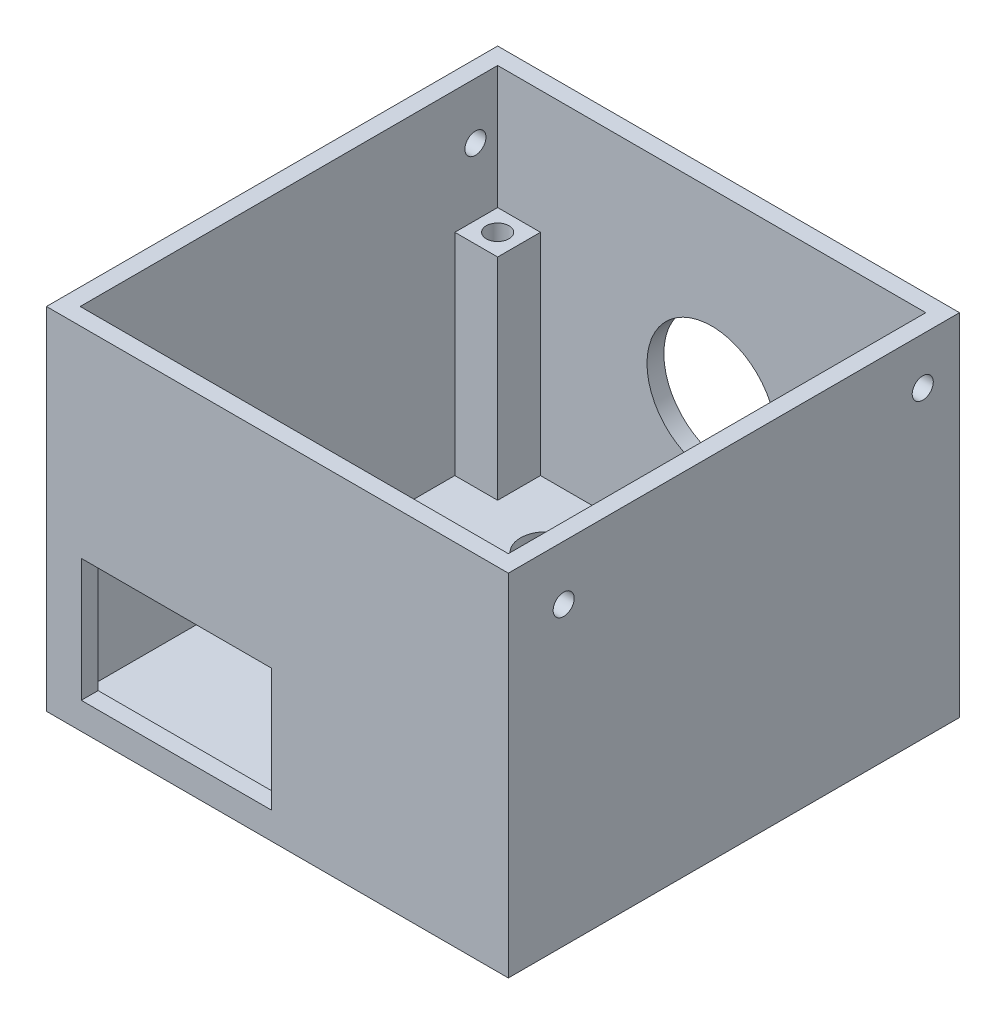
SolidWorks part; units mm, degrees
ref_plane "Front Plane" through (0, 0, 0) normal (0, 0, 1) x (1, 0, 0)
ref_plane "Top Plane" through (0, 0, 0) normal (0, 1, 0) x (1, 0, 0)
ref_plane "Right Plane" through (0, 0, 0) normal (1, 0, 0) x (0, 0, -1)
sketch "Sketch1" plane through (0, 0, 0) normal (0, 1, 0) x (1, 0, 0)
  line L1 (27.4, -26.765) -> (-27.4, -26.765)
  line L2 (27.4, -26.765) -> (27.4, 26.765)
  line L3 (27.4, 26.765) -> (-27.4, 26.765)
  line L4 (-27.4, -26.765) -> (-27.4, 26.765)
  line L5 (27.4, -26.765) -> (-27.4, 26.765) construction
  line L6 (27.4, 26.765) -> (-27.4, -26.765) construction
  point P0 (0, 0)
  dimension "D1" = 54.8
  dimension "D2" = 53.53
extrude "Boss-Extrude1" add sketch "Sketch1" along normal blind 41.6
sketch "Sketch2" plane through (0, 41.6, 0) normal (0, 1, 0) x (1, 0, 0)
  line L0 (-27.4, 26.765) -> (-27.4, -26.765) construction
  line L1 (25.4, -24.765) -> (-25.4, -24.765)
  line L2 (25.4, -24.765) -> (25.4, 24.765)
  line L3 (25.4, 24.765) -> (-25.4, 24.765)
  line L4 (-25.4, -24.765) -> (-25.4, 24.765)
  line L5 (25.4, -24.765) -> (-25.4, 24.765) construction
  line L6 (25.4, 24.765) -> (-25.4, -24.765) construction
  line L7 (27.4, 26.765) -> (-27.4, 26.765) construction
  point P0 (0, 0)
  dimension "D1" = 2
  dimension "D2" = 2
extrude "Cut-Extrude1" cut sketch "Sketch2" against normal blind 39.6
sketch "Sketch3" plane through (0, 2, 0) normal (0, 1, 0) x (1, 0, 0)
  line L1 (-25.4, 24.765) -> (-20.32, 24.765)
  line L2 (-25.4, 24.765) -> (-25.4, 19.685)
  line L3 (-25.4, 19.685) -> (-20.32, 19.685)
  line L4 (-20.32, 24.765) -> (-20.32, 19.685)
  line L5 (25.4, 24.765) -> (20.32, 24.765)
  line L6 (25.4, 24.765) -> (25.4, 19.685)
  line L7 (25.4, 19.685) -> (20.32, 19.685)
  line L8 (20.32, 24.765) -> (20.32, 19.685)
  line L9 (25.4, -24.765) -> (20.32, -24.765)
  line L10 (25.4, -24.765) -> (25.4, -19.685)
  line L11 (25.4, -19.685) -> (20.32, -19.685)
  line L12 (20.32, -24.765) -> (20.32, -19.685)
  dimension "D1" = 5.08
  dimension "D2" = 5.08
  dimension "D3" = 5.08
  dimension "D4" = 5.08
  dimension "D5" = 5.08
  dimension "D6" = 5.08
extrude "Boss-Extrude2" add sketch "Sketch3" along normal blind 25
sketch "Sketch4" plane through (0, 27, 0) normal (0, 1, 0) x (1, 0, 0)
  line L0 (-20.32, 19.685) -> (-20.32, 24.765) construction
  line L3 (-25.4, 19.685) -> (-20.32, 19.685) construction
  line L4 (20.32, 19.685) -> (25.4, 19.685) construction
  line L5 (20.32, 24.765) -> (20.32, 19.685) construction
  line L6 (25.4, -19.685) -> (20.32, -19.685) construction
  line L7 (20.32, -19.685) -> (20.32, -24.765) construction
  circle A0 centre (-22.86, 22.225) radius 1.35
  circle A1 centre (22.86, 22.225) radius 1.35
  circle A2 centre (22.86, -22.225) radius 1.35
  point P12 (22.86, -19.685)
  dimension "D1" = 2.54
  dimension "D3" = 2.54
  dimension "D5" = 2.54
  dimension "D2" = 2.54
  dimension "D4" = 2.54
  dimension "D6" = 2.54
extrude "Cut-Extrude2" cut sketch "Sketch4" against normal blind 10
sketch "Sketch5" plane through (0, 0, 0) normal (0, -1, 0) x (-1, 0, 0)
  circle A0 centre (-12.7629, 17.1869) radius 3
  circle A1 centre (12.1084, 17.1869) radius 3
extrude "Cut-Extrude3" cut sketch "Sketch5" against normal up to next
sketch "Sketch6" plane through (0, 0, 0) normal (0, -1, 0) x (-1, 0, 0)
  circle A0 centre (-16.9081, 1.5272) radius 3.1
  circle A1 centre (-8.7267, 1.5272) radius 3.1
extrude "Cut-Extrude4" cut sketch "Sketch6" against normal up to next
sketch "Sketch7" plane through (0, 0, 0) normal (0, -1, 0) x (-1, 0, 0)
  circle A0 centre (-12.6538, -10.0358) radius 3.6
extrude "Cut-Extrude5" cut sketch "Sketch7" against normal up to next
sketch "Sketch8" plane through (27.4, 0, 0) normal (1, 0, 0) x (0, 0, -1)
  circle A0 centre (-20.2009, 35.1133) radius 1.25
extrude "Cut-Extrude6" cut sketch "Sketch8" against normal up to next
sketch "Sketch10" plane through (-27.4, 0, 0) normal (-1, 0, 0) x (0, 0, 1)
  circle A0 centre (-22.1268, 34.9354) radius 1.25
extrude "Cut-Extrude7" cut sketch "Sketch10" against normal up to next
sketch "Sketch12" plane through (0, 0, -26.765) normal (0, 0, -1) x (-1, 0, 0)
  circle A0 centre (0, 19.8508) radius 7.6805
extrude "Cut-Extrude8" cut sketch "Sketch12" against normal up to next
sketch "Sketch13" plane through (0, 0, 26.765) normal (0, 0, 1) x (1, 0, 0)
  line L1 (-0.6897, 3.1964) -> (-23.2715, 3.1964)
  line L2 (-0.6897, 3.1964) -> (-0.6897, 17.7861)
  line L3 (-0.6897, 17.7861) -> (-23.2715, 17.7861)
  line L4 (-23.2715, 3.1964) -> (-23.2715, 17.7861)
  line L5 (-0.6897, 3.1964) -> (-23.2715, 17.7861) construction
  line L6 (-0.6897, 17.7861) -> (-23.2715, 3.1964) construction
  point P0 (-11.9806, 10.4912)
extrude "Cut-Extrude9" cut sketch "Sketch13" against normal up to next
sketch "Sketch14" plane through (27.4, 0, 0) normal (1, 0, 0) x (0, 0, -1)
  circle A0 centre (22.4032, 36.0407) radius 1.25
extrude "Cut-Extrude10" cut sketch "Sketch14" against normal up to next
